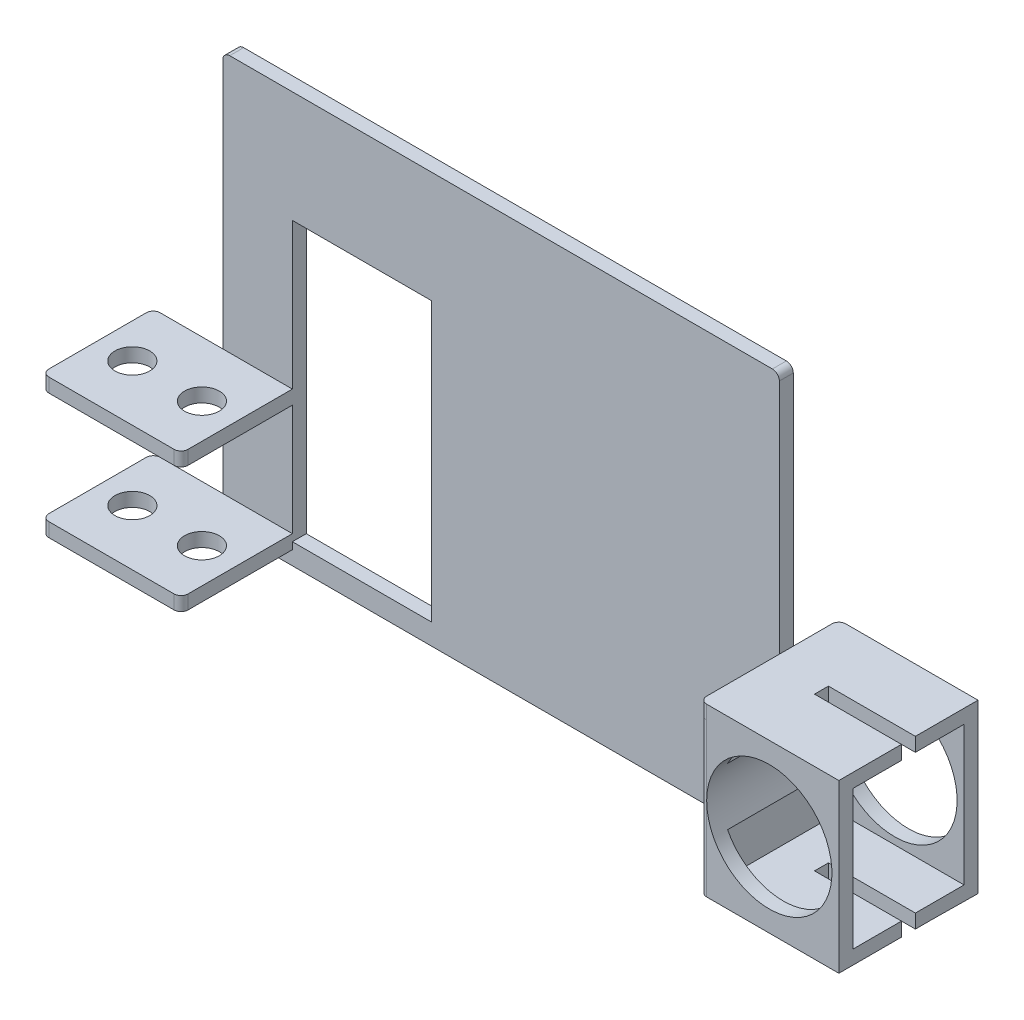
SolidWorks part; units mm, degrees
ref_plane "Front Plane" through (0, 0, 0) normal (0, 0, 1) x (1, 0, 0)
ref_plane "Top Plane" through (0, 0, 0) normal (0, 1, 0) x (1, 0, 0)
ref_plane "Right Plane" through (0, 0, 0) normal (1, 0, 0) x (0, 0, -1)
sketch "Sketch1" plane through (0, 0, 0) normal (0, 1, 0) x (1, 0, 0)
  line L0 (-2.2917, 11.0417) -> (-22.2917, 11.0417)
  line L1 (-22.2917, 11.0417) -> (-22.2917, -8.9583)
  line L2 (-22.2917, -8.9583) -> (-2.2917, -8.9583)
  line L3 (-20.2917, 9.0417) -> (-2.2917, 9.0417)
  line L4 (-20.2917, 9.0417) -> (-20.2917, -6.9583)
  line L5 (-20.2917, -6.9583) -> (-2.2917, -6.9583)
  line L6 (-2.2917, -6.9583) -> (-2.2917, -8.9583)
  line L7 (-2.2917, 9.0417) -> (-2.2917, 11.0417)
  dimension "D1" = 20
  dimension "D2" = 20
  dimension "D3" = 20
  dimension "D4" = 2
  dimension "D5" = 2
  dimension "D6" = 2
extrude "Boss-Extrude1" add sketch "Sketch1" along normal blind 20
fillet "Fillet1" radius 1 2 edges at (-22.2917, 10, -11.0417) (-22.2917, 10, 8.9583)
sketch "Sketch2" plane through (0, 0, 8.9583) normal (0, 0, 1) x (1, 0, 0)
  line L0 (-21.2917, 0) -> (-2.2917, 0) construction
  line L1 (-2.2917, 20) -> (-2.2917, 0) construction
  circle A0 centre (-12.2917, 10) radius 9
  dimension "D3" = 18
  dimension "D1" = 10
  dimension "D2" = 10
extrude "Cut-Extrude1" cut sketch "Sketch2" against normal blind 20
sketch "Sketch3" plane through (0, 20, 0) normal (0, 1, 0) x (1, 0, 0)
  line L0 (-21.2917, 11.0417) -> (-2.2917, 11.0417)
  line L1 (-2.2917, 11.0417) -> (-2.2917, -8.9583)
  line L2 (-2.2917, -8.9583) -> (-22.2917, -8.9583)
  line L3 (-22.2917, -8.9583) -> (-22.2917, 11.0417)
  line L4 (-22.2917, 11.0417) -> (-21.2917, 11.0417)
  line L9 (-2.2917, 2.3778) -> (-2.2917, 0.3778)
  line M10 (-2.2917, 11.0417) -> (-21.2917, 11.0417)
  arc M11 (-21.2917, 11.0417) -> (-22.2917, 10.0417) centre (-21.2917, 10.0417) ccw
  line M12 (-22.2917, 10.0417) -> (-22.2917, -7.9583)
  arc M13 (-22.2917, -7.9583) -> (-21.2917, -8.9583) centre (-21.2917, -7.9583) ccw
  line M14 (-21.2917, -8.9583) -> (-2.2917, -8.9583)
  line M15 (-2.2917, -8.9583) -> (-2.2917, -6.9583)
  line M16 (-2.2917, -6.9583) -> (-20.2917, -6.9583)
  line M17 (-20.2917, -6.9583) -> (-20.2917, 9.0417)
  line M18 (-20.2917, 9.0417) -> (-2.2917, 9.0417)
  line M19 (-2.2917, 9.0417) -> (-2.2917, 11.0417)
  dimension "D1" = 20
extrude "Boss-Extrude2" add sketch "Sketch3" along normal blind 2 contours L1 M18 M17 M16 | M19 M10 M11 M12 M13 M14 M15 M16 M17 M18 region at (-11.7917, 20, -10.7588) region at (-11.2917, 20, -1.0417)
sketch "Sketch4" plane through (0, 0, 0) normal (0, -1, 0) x (1, 0, 0)
  line L0 (-2.2917, 8.9583) -> (-2.2917, -11.0417)
  line L1 (-2.2917, -11.0417) -> (-22.2917, -11.0417)
  line L2 (-22.2917, -11.0417) -> (-22.2917, 8.9583)
  line L3 (-22.2917, 8.9583) -> (-2.2917, 8.9583)
  dimension "D1" = 20
  dimension "D2" = 20
extrude "Boss-Extrude3" add sketch "Sketch4" along normal blind 2
fillet "Fillet2" radius 1 2 edges at (-22.2917, -1, -11.0417) (-22.2917, -1, 8.9583)
sketch "Sketch5" plane through (0, 22, 0) normal (0, 1, 0) x (1, 0, 0)
  line L0 (-2.2917, 11.0417) -> (-2.2917, -8.9583) construction
  line L1 (-14.7917, 2.0417) -> (-2.2917, 2.0417)
  line L2 (-14.7917, 2.0417) -> (-14.7917, 0.0417)
  line L3 (-14.7917, 0.0417) -> (-2.2917, 0.0417)
  line L4 (-2.2917, 2.0417) -> (-2.2917, 0.0417)
  line L5 (-21.2917, -8.9583) -> (-2.2917, -8.9583) construction
  dimension "D1" = 12.5
  dimension "D2" = 2
  dimension "D3" = 9
extrude "Cut-Extrude2" cut sketch "Sketch5" against normal blind 24
sketch "Sketch6" plane through (-22.2917, 0, 0) normal (-1, 0, 0) x (0, 0, 1)
  line L0 (-2.4917, -37) -> (-4.4917, -37)
  line L5 (-4.4917, -37) -> (-4.4917, -2)
  line L6 (-10.0417, 22) -> (7.9583, 22) construction
  line L7 (-2.4917, 22) -> (-4.4917, 22)
  line L8 (-2.4917, 22) -> (-2.4917, -2)
  line L10 (-4.4917, 22) -> (-4.4917, -2)
  line L11 (7.9583, -2) -> (-10.0417, -2) construction
  line L12 (-11.0417, 10) -> (-11.0417, 22) construction
  line L13 (-2.4917, -2) -> (-2.4917, -37)
  point P6 (-3.4917, -37)
  dimension "D1" = 6.55
  dimension "D2" = 2
  dimension "D3" = 35
extrude "Boss-Extrude4" add sketch "Sketch6" along normal blind 80
fillet "Fillet3" radius 1 3 edges at (-22.2917, -37, -3.4917) (-102.2917, -37, -3.4917) (-102.2917, 22, -3.4917)
sketch "Sketch8" plane through (0, 0, -4.4917) normal (0, 0, -1) x (-1, 0, 0)
  line L0 (82.2917, 22) -> (82.2917, -40.0805) construction
  line L1 (72.2917, 19) -> (92.2917, 19)
  line L2 (72.2917, 19) -> (72.2917, -21)
  line L3 (72.2917, -21) -> (92.2917, -21)
  line L4 (92.2917, 19) -> (92.2917, -21)
  line L5 (101.2917, 22) -> (22.2917, 22) construction
  line L6 (12.2917, 10) -> (131.172, 10) construction
  circle A0 centre (12.2917, 10) radius 9 construction
  circle A1 centre (12.2917, 10) radius 7.1139
  dimension "D4" = 70
  dimension "D1" = 20
  dimension "D2" = 40
  dimension "D3" = 10
  dimension "D5" = 9
extrude "Cut-Extrude3" cut sketch "Sketch8" against normal blind 2
sketch "Sketch9" plane through (0, 0, -2.4917) normal (0, 0, 1) x (1, 0, 0)
  line L0 (-92.824, 20) -> (-112.2917, 20)
  line L1 (-112.2917, 20) -> (-112.2917, 18)
  line L2 (-112.2917, 18) -> (-92.2917, 18)
  line L3 (-92.2917, -21) -> (-92.2917, 19) construction
  line L4 (-92.2917, 18) -> (-92.2917, 20)
  line L5 (-92.2917, 20) -> (-92.824, 20)
  line L6 (-92.2917, 0) -> (-92.2917, 2)
  line L7 (-92.2917, 2) -> (-112.2917, 2)
  line L8 (-112.2917, 2) -> (-112.2917, 0)
  line L9 (-112.2917, 0) -> (-92.2917, 0)
  line L10 (-101.2917, 22) -> (-22.2917, 22) construction
  point P13 (-112.2917, 1)
  dimension "D1" = 2
  dimension "D2" = 2
  dimension "D3" = 2
  dimension "D4" = 16
  dimension "D5" = 20
  dimension "D6" = 20
extrude "Boss-Extrude5" add sketch "Sketch9" along normal blind 16
fillet "Fillet4" radius 1 6 edges at (-112.2917, 1, -2.4917) (-112.2917, 19, -2.4917) (-112.2917, 1, 13.5083) (-92.2917, 1, 13.5083) (-92.2917, 19, 13.5083) (-112.2917, 19, 13.5083)
sketch "Sketch10" plane through (0, 20, 0) normal (0, 1, 0) x (1, 0, 0)
  line L0 (-102.2917, 2.4917) -> (-111.2917, 2.4917) construction
  line L1 (-92.2917, 2.4917) -> (-102.2917, 2.4917) construction
  line L2 (-92.2917, -12.5083) -> (-92.2917, 2.4917) construction
  circle A0 centre (-97.2917, -5.5083) radius 2.5
  circle A1 centre (-107.2917, -5.5083) radius 2.5
  dimension "D1" = 5
  dimension "D2" = 5
  dimension "D3" = 10
  dimension "D4" = 8
  dimension "D5" = 8
  dimension "D6" = 5
extrude "Cut-Extrude4" cut sketch "Sketch10" against normal blind 20
mirror "Mirror18" about plane through (0, 22, 0) normal (0, 1, 0) of bodies 109
sketch "Sketch15" plane through (-102.2917, 0, 0) normal (-1, 0, 0) x (0, 0, 1)
  line L0 (-4.4917, 22) -> (26.3712, 22)
  line L1 (-4.4917, 46) -> (-4.4917, -2) construction
  line L2 (26.3712, 22) -> (26.3712, -60.2251)
  line L3 (26.3712, -60.2251) -> (-46.7014, -60.2251)
  line L4 (-46.7014, -60.2251) -> (-46.7014, 21.5)
  line L5 (-46.7014, 21.5) -> (-4.4917, 22)
extrude "Cut-Extrude5" cut sketch "Sketch15" against normal blind 1000
sketch "Sketch16" plane through (-102.2917, 0, 0) normal (1, 0, 0) x (0, 0, -1)
  line L1 (-27.768, 21.983) -> (17.1564, 21.983)
  line L2 (-27.768, 21.983) -> (-27.768, -6.7788)
  line L3 (-27.768, -6.7788) -> (17.1564, -6.7788)
  line L4 (17.1564, 21.983) -> (17.1564, -6.7788)
extrude "Cut-Extrude6" cut sketch "Sketch16" against normal blind 200
